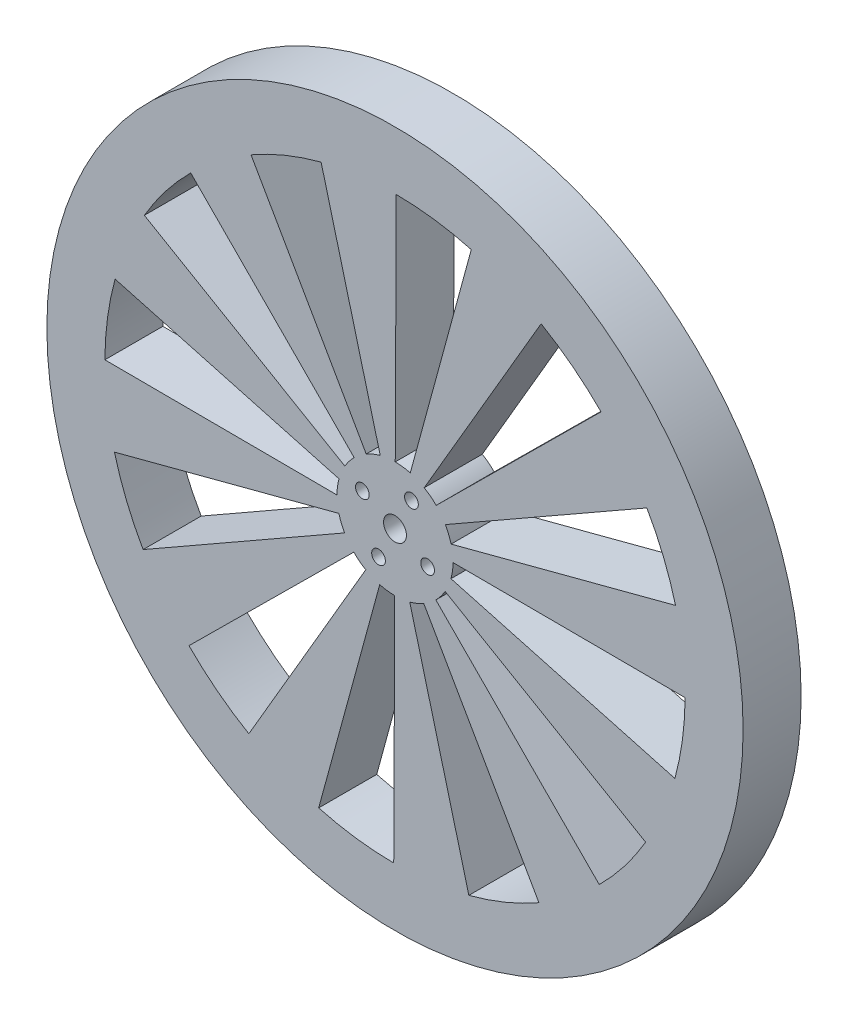
SolidWorks part; units mm, degrees
ref_plane "Front Plane" through (0, 0, 0) normal (0, 0, 1) x (1, 0, 0)
ref_plane "Top Plane" through (0, 0, 0) normal (0, 1, 0) x (1, 0, 0)
ref_plane "Right Plane" through (0, 0, 0) normal (1, 0, 0) x (0, 0, -1)
sketch "Sketch2" plane through (0, 0, 0) normal (0, 0, 1) x (1, 0, 0)
  circle A0 centre (0, 0) radius 76.2
  dimension "D1" = 152.4
extrude "Boss-Extrude1" add sketch "Sketch2" along normal blind 12.7
sketch "Sketch5" plane through (0, 0, 12.7) normal (0, 0, 1) x (1, 0, 0)
  line L0 (0.0548, 12.6999) -> (0.2739, 63.4994)
  line L1 (3.3399, 12.253) -> (16.6994, 61.2648)
  line L2 (9.0189, 8.9414) -> (45.0945, 44.7072)
  line L3 (6.3974, 10.971) -> (31.9869, 54.8552)
  line L4 (12.2813, 3.2341) -> (61.4066, 16.1703)
  line L5 (11.0258, 6.3025) -> (55.1291, 31.5125)
  line L6 (12.253, -3.3399) -> (61.2648, -16.6994)
  line L7 (12.6999, -0.0548) -> (63.4994, -0.2739)
  line L8 (8.9414, -9.0189) -> (44.7072, -45.0945)
  line L9 (10.971, -6.3974) -> (54.8552, -31.9869)
  line L10 (3.2341, -12.2813) -> (16.1703, -61.4066)
  line L11 (6.3025, -11.0258) -> (31.5125, -55.1291)
  line L12 (-3.3399, -12.253) -> (-16.6994, -61.2648)
  line L13 (-0.0548, -12.6999) -> (-0.2739, -63.4994)
  line L14 (-9.0189, -8.9414) -> (-45.0945, -44.7072)
  line L15 (-6.3974, -10.971) -> (-31.9869, -54.8552)
  line L16 (-12.2813, -3.2341) -> (-61.4066, -16.1703)
  line L17 (-11.0258, -6.3025) -> (-55.1291, -31.5125)
  line L18 (-12.253, 3.3399) -> (-61.2648, 16.6994)
  line L19 (-12.6999, 0.0548) -> (-63.4994, 0.2739)
  line L20 (-8.9414, 9.0189) -> (-44.7072, 45.0945)
  line L21 (-10.971, 6.3974) -> (-54.8552, 31.9869)
  line L22 (-3.2341, 12.2813) -> (-16.1703, 61.4066)
  line L23 (-6.3025, 11.0258) -> (-31.5125, 55.1291)
  arc A0 (-12.253, 3.3399) -> (-12.6999, 0.0548) centre (0, 0) ccw
  arc A1 (-44.7072, 45.0945) -> (-54.8552, 31.9869) centre (0, 0) ccw
  arc A2 (-61.2648, 16.6994) -> (-63.4994, 0.2739) centre (0, 0) ccw
  arc A3 (-61.4066, -16.1703) -> (-55.1291, -31.5125) centre (0, 0) ccw
  arc A4 (-45.0945, -44.7072) -> (-31.9869, -54.8552) centre (0, 0) ccw
  arc A5 (-16.6994, -61.2648) -> (-0.2739, -63.4994) centre (0, 0) ccw
  arc A6 (16.1703, -61.4066) -> (31.5125, -55.1291) centre (0, 0) ccw
  arc A7 (44.7072, -45.0945) -> (54.8552, -31.9869) centre (0, 0) ccw
  arc A8 (61.2648, -16.6994) -> (63.4994, -0.2739) centre (0, 0) ccw
  arc A9 (61.4066, 16.1703) -> (55.1291, 31.5125) centre (0, 0) ccw
  arc A10 (-16.1703, 61.4066) -> (-31.5125, 55.1291) centre (0, 0) ccw
  arc A11 (16.6994, 61.2648) -> (0.2739, 63.4994) centre (0, 0) ccw
  arc A12 (45.0945, 44.7072) -> (31.9869, 54.8552) centre (0, 0) ccw
  arc A13 (-8.9414, 9.0189) -> (-10.971, 6.3974) centre (0, 0) ccw
  arc A14 (-3.2341, 12.2813) -> (-6.3025, 11.0258) centre (0, 0) ccw
  arc A15 (3.3399, 12.253) -> (0.0548, 12.6999) centre (0, 0) ccw
  arc A16 (9.0189, 8.9414) -> (6.3974, 10.971) centre (0, 0) ccw
  arc A17 (12.2813, 3.2341) -> (11.0258, 6.3025) centre (0, 0) ccw
  arc A18 (12.253, -3.3399) -> (12.6999, -0.0548) centre (0, 0) ccw
  arc A19 (8.9414, -9.0189) -> (10.971, -6.3974) centre (0, 0) ccw
  arc A20 (3.2341, -12.2813) -> (6.3025, -11.0258) centre (0, 0) ccw
  arc A21 (-3.3399, -12.253) -> (-0.0548, -12.6999) centre (0, 0) ccw
  arc A22 (-9.0189, -8.9414) -> (-6.3974, -10.971) centre (0, 0) ccw
  arc A23 (-12.2813, -3.2341) -> (-11.0258, -6.3025) centre (0, 0) ccw
  point P31 (0, 0)
  dimension "D1" = 25.4
  dimension "D2" = 127
  dimension "D3" = 15
  dimension "D5" = 61.2648
  dimension "D4" = 12
extrude "Cut-Extrude4" cut sketch "Sketch5" against normal through all
sketch "Sketch4" plane through (0, 0, 12.7) normal (0, 0, 1) x (1, 0, 0)
  circle A0 centre (0, 0) radius 8 construction
  circle A1 centre (3.6051, 7.1417) radius 1.5
  point P14 (0, 0)
  dimension "D1" = 16
  dimension "D2" = 3
  dimension "D3" = 7.1417
extrude "Cut-Extrude2" cut sketch "Sketch4" against normal through all
pattern_circular "CirPattern1" count 4 over 360 about axis through (0, 0, 0) along (0, 0, 1) of "Cut-Extrude2" reverse direction yes
sketch "Sketch6" plane through (0, 0, 12.7) normal (0, 0, 1) x (1, 0, 0)
  circle A0 centre (0, 0) radius 2.5
  dimension "D1" = 5
extrude "Cut-Extrude5" cut sketch "Sketch6" against normal through all
